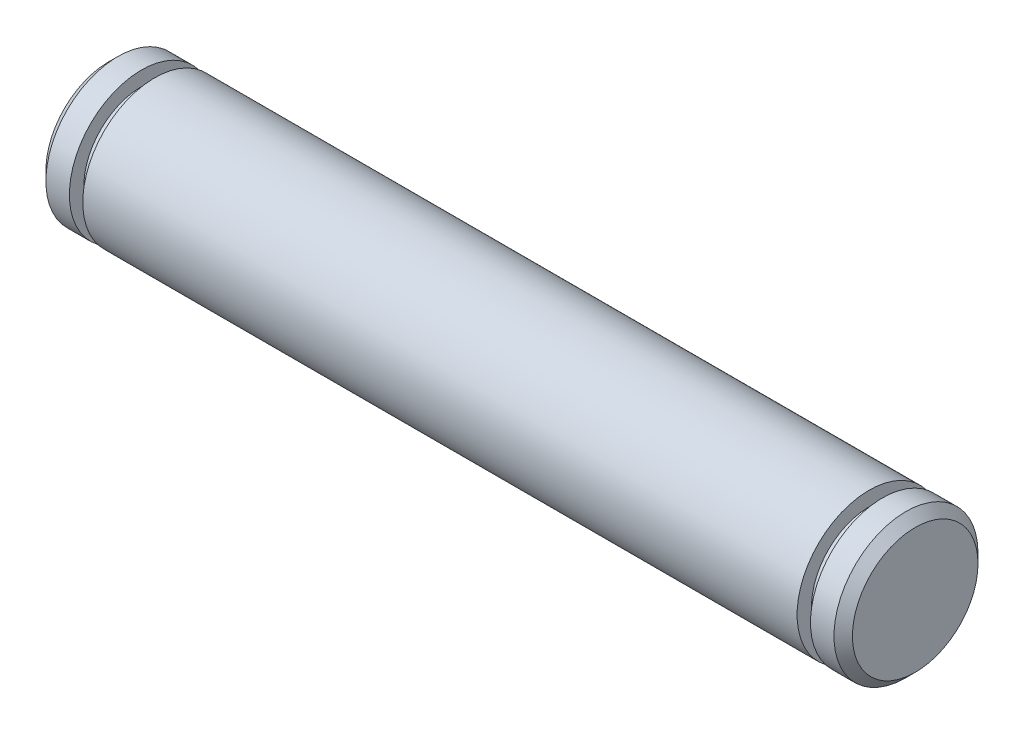
SolidWorks part; units mm, degrees
ref_plane "Front Plane" through (0, 0, 0) normal (0, 0, 1) x (1, 0, 0)
ref_plane "Top Plane" through (0, 0, 0) normal (0, 1, 0) x (1, 0, 0)
ref_plane "Right Plane" through (0, 0, 0) normal (1, 0, 0) x (0, 0, -1)
sketch "Sketch1" plane through (0, 0, 0) normal (1, 0, 0) x (0, 0, -1)
  circle A0 centre (0, 0) radius 3.9688
  dimension "D1" = 7.9375
extrude "Boss-Extrude1" add sketch "Sketch1" along normal mid plane 44.45
chamfer "Chamfer1" distance 0.508 angle 45 2 edges at (-22.225, 0, -3.9688) (22.225, 0, -3.9688)
ref_plane "Plane1" through (19.685, 0, 0) normal (1, 0, 0) x (0, 0, -1)
sketch "Sketch2" plane through (19.685, 0, 0) normal (1, 0, 0) x (0, 0, -1)
  circle A0 centre (0, 0) radius 3.9688 construction
  circle A1 centre (0, 0) radius 3.9688
  circle A2 centre (0, 0) radius 3.175
  dimension "D1" = 6.35
extrude "Cut-Extrude1" cut sketch "Sketch2" along normal blind 0.7366
mirror "Mirror1" about plane through (0, 0, 0) normal (1, 0, 0) of "Cut-Extrude1"
